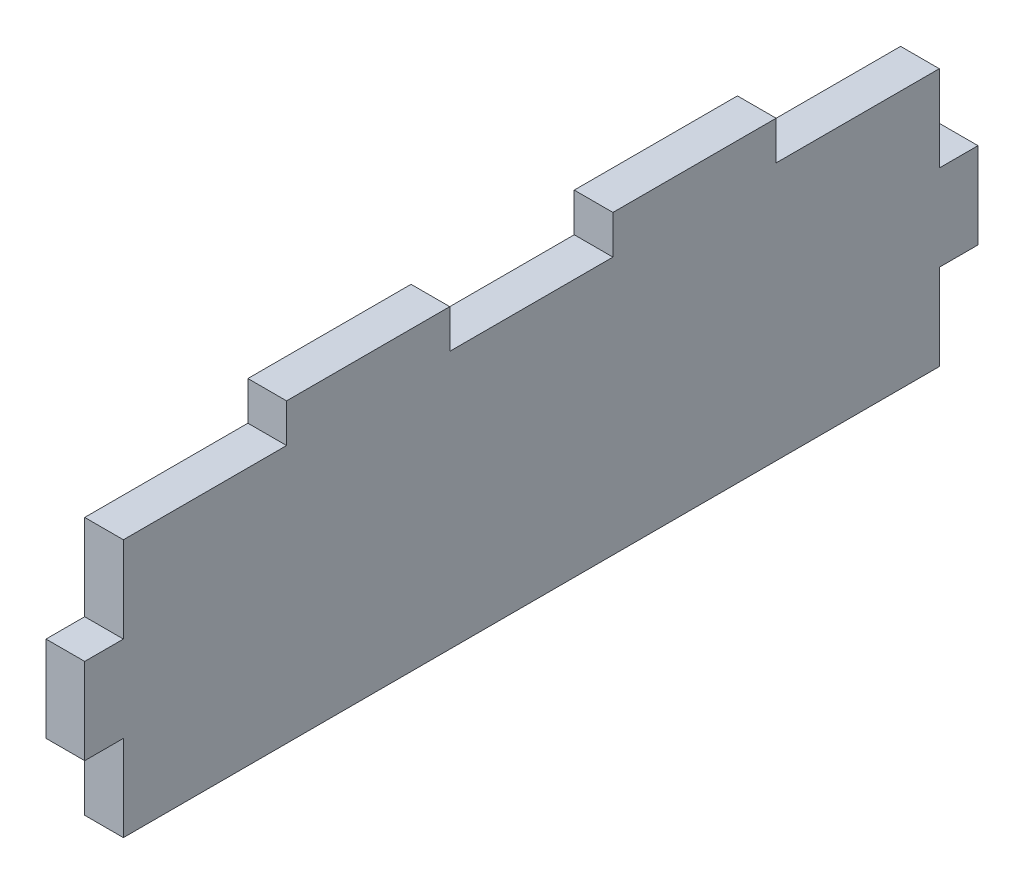
SolidWorks part; units mm, degrees
ref_plane "Front Plane" through (0, 0, 0) normal (0, 0, 1) x (1, 0, 0)
ref_plane "Top Plane" through (0, 0, 0) normal (0, 1, 0) x (1, 0, 0)
ref_plane "Right Plane" through (0, 0, 0) normal (1, 0, 0) x (0, 0, -1)
sketch "Sketch1" plane through (0, 0, 0) normal (0, 1, 0) x (1, 0, 0)
  line L1 (-207.5, -63.25) -> (207.5, -63.25)
  line L2 (-207.5, -63.25) -> (-207.5, 63.25)
  line L3 (-207.5, 63.25) -> (207.5, 63.25)
  line L4 (207.5, -63.25) -> (207.5, 63.25)
  line L5 (-207.5, -63.25) -> (207.5, 63.25) construction
  line L6 (-207.5, 63.25) -> (207.5, -63.25) construction
  point P0 (0, 0)
  dimension "D1" = 126.5
  dimension "D2" = 415
extrude "Boss-Extrude1" add sketch "Sketch1" along normal blind 6
sketch "Sketch2" plane through (0, 6, 0) normal (0, 1, 0) x (1, 0, 0)
  line L0 (213.5, -69.25) -> (213.5, 69.25)
  line L3 (-213.5, -69.25) -> (213.5, -69.25)
  line L4 (207.5, -63.25) -> (207.5, 63.25)
  line L5 (207.5, 63.25) -> (-207.5, 63.25)
  line L6 (-207.5, 63.25) -> (-207.5, -63.25)
  line L7 (-207.5, -63.25) -> (207.5, -63.25)
  line L8 (207.5, -63.25) -> (207.5, 63.25)
  line L9 (207.5, 63.25) -> (-207.5, 63.25)
  line L10 (-207.5, 63.25) -> (-207.5, -63.25)
  line L11 (-207.5, -63.25) -> (207.5, -63.25)
  line L12 (231.5, -87.25) -> (231.5, 87.25)
  line L13 (231.5, 87.25) -> (-231.5, 87.25)
  line L14 (-231.5, 87.25) -> (-231.5, -87.25)
  line L15 (-231.5, -87.25) -> (231.5, -87.25)
  line L16 (237.5, -93.25) -> (237.5, 93.25)
  line L19 (-237.5, -93.25) -> (237.5, -93.25)
  line L20 (213.5, 69.25) -> (-213.5, 69.25) construction
  line L21 (-213.5, 69.25) -> (-213.5, -69.25) construction
  line L22 (-213.5, -69.25) -> (-213.5, -63.25)
  line L27 (152.5, 69.25) -> (91.5, 69.25)
  line L28 (152.5, 69.25) -> (152.5, 63.25)
  line L29 (152.5, 63.25) -> (91.5, 63.25)
  line L30 (91.5, 69.25) -> (91.5, 63.25)
  line L31 (91.5, 69.25) -> (30.5, 69.25)
  line L32 (91.5, 69.25) -> (91.5, 63.25)
  line L33 (91.5, 63.25) -> (30.5, 63.25)
  line L34 (30.5, 69.25) -> (30.5, 63.25)
  line L35 (30.5, 69.25) -> (-30.5, 69.25)
  line L36 (30.5, 69.25) -> (30.5, 63.25)
  line L37 (30.5, 63.25) -> (-30.5, 63.25)
  line L38 (-30.5, 69.25) -> (-30.5, 63.25)
  line L39 (-30.5, 69.25) -> (-91.5, 69.25)
  line L40 (-30.5, 69.25) -> (-30.5, 63.25)
  line L41 (-30.5, 63.25) -> (-91.5, 63.25)
  line L42 (-91.5, 69.25) -> (-91.5, 63.25)
  line L43 (-91.5, 69.25) -> (-152.5, 69.25)
  line L44 (-91.5, 69.25) -> (-91.5, 63.25)
  line L45 (-91.5, 63.25) -> (-152.5, 63.25)
  line L46 (-152.5, 69.25) -> (-152.5, 63.25)
  line L47 (-152.5, 69.25) -> (-213.5, 69.25)
  line L48 (-152.5, 69.25) -> (-152.5, 63.25)
  line L49 (-152.5, 63.25) -> (-213.5, 63.25)
  line L50 (-213.5, 69.25) -> (-213.5, 63.25)
  line L51 (-213.5, 63.25) -> (-207.5, 63.25)
  line L52 (-213.5, 63.25) -> (-213.5, 37.95)
  line L53 (-213.5, 37.95) -> (-207.5, 37.95)
  line L54 (-207.5, 63.25) -> (-207.5, 37.95)
  line L55 (-207.5, 37.95) -> (-213.5, 37.95)
  line L56 (-207.5, 37.95) -> (-207.5, 12.65)
  line L57 (-207.5, 12.65) -> (-213.5, 12.65)
  line L58 (-213.5, 37.95) -> (-213.5, 12.65)
  line L59 (-213.5, 12.65) -> (-207.5, 12.65)
  line L60 (-213.5, 12.65) -> (-213.5, -12.65)
  line L61 (-213.5, -12.65) -> (-207.5, -12.65)
  line L62 (-207.5, 12.65) -> (-207.5, -12.65)
  line L63 (-207.5, -12.65) -> (-213.5, -12.65)
  line L64 (-207.5, -12.65) -> (-207.5, -37.95)
  line L65 (-207.5, -37.95) -> (-213.5, -37.95)
  line L66 (-213.5, -12.65) -> (-213.5, -37.95)
  line L67 (-213.5, -37.95) -> (-207.5, -37.95)
  line L68 (-213.5, -37.95) -> (-213.5, -63.25)
  line L69 (-213.5, -63.25) -> (-207.5, -63.25)
  line L70 (-207.5, -37.95) -> (-207.5, -63.25)
  line L71 (152.5, 63.25) -> (213.5, 63.25)
  line L72 (152.5, 63.25) -> (152.5, 69.25)
  line L73 (152.5, 69.25) -> (213.5, 69.25)
  line L74 (213.5, 63.25) -> (213.5, 69.25)
  line L75 (-237.5, 93.25) -> (-231.5, 93.25)
  line L76 (-237.5, 93.25) -> (-237.5, 55.95)
  line L77 (-237.5, 55.95) -> (-231.5, 55.95)
  line L78 (-231.5, 93.25) -> (-231.5, 55.95)
  line L79 (-237.5, 93.25) -> (-237.5, -93.25) construction
  line L80 (-231.5, 55.95) -> (-237.5, 55.95)
  line L81 (-231.5, 55.95) -> (-231.5, 18.65)
  line L82 (-231.5, 18.65) -> (-237.5, 18.65)
  line L83 (-237.5, 55.95) -> (-237.5, 18.65)
  line L84 (-237.5, 18.65) -> (-231.5, 18.65)
  line L85 (-237.5, 18.65) -> (-237.5, -18.65)
  line L86 (-237.5, -18.65) -> (-231.5, -18.65)
  line L87 (-231.5, 18.65) -> (-231.5, -18.65)
  line L88 (-231.5, -18.65) -> (-237.5, -18.65)
  line L89 (-231.5, -18.65) -> (-231.5, -55.95)
  line L90 (-231.5, -55.95) -> (-237.5, -55.95)
  line L91 (-237.5, -18.65) -> (-237.5, -55.95)
  line L92 (-237.5, -55.95) -> (-231.5, -55.95)
  line L93 (-237.5, -55.95) -> (-237.5, -93.25)
  line L94 (-237.5, -93.25) -> (-231.5, -93.25)
  line L95 (-231.5, -55.95) -> (-231.5, -93.25)
  line L96 (231.5, 87.25) -> (165.3571, 87.25)
  line L97 (231.5, 87.25) -> (231.5, 93.25)
  line L98 (231.5, 93.25) -> (165.3571, 93.25)
  line L99 (165.3571, 87.25) -> (165.3571, 93.25)
  line L100 (165.3571, 93.25) -> (99.2143, 93.25)
  line L101 (165.3571, 93.25) -> (165.3571, 87.25)
  line L102 (165.3571, 87.25) -> (99.2143, 87.25)
  line L103 (99.2143, 93.25) -> (99.2143, 87.25)
  line L104 (99.2143, 87.25) -> (33.0714, 87.25)
  line L105 (99.2143, 87.25) -> (99.2143, 93.25)
  line L106 (99.2143, 93.25) -> (33.0714, 93.25)
  line L107 (33.0714, 87.25) -> (33.0714, 93.25)
  line L108 (33.0714, 93.25) -> (-33.0714, 93.25)
  line L109 (33.0714, 93.25) -> (33.0714, 87.25)
  line L110 (33.0714, 87.25) -> (-33.0714, 87.25)
  line L111 (-33.0714, 93.25) -> (-33.0714, 87.25)
  line L112 (-33.0714, 87.25) -> (-99.2143, 87.25)
  line L113 (-33.0714, 87.25) -> (-33.0714, 93.25)
  line L114 (-33.0714, 93.25) -> (-99.2143, 93.25)
  line L115 (-99.2143, 87.25) -> (-99.2143, 93.25)
  line L116 (-99.2143, 93.25) -> (-165.3571, 93.25)
  line L117 (-99.2143, 93.25) -> (-99.2143, 87.25)
  line L118 (-99.2143, 87.25) -> (-165.3571, 87.25)
  line L119 (-165.3571, 93.25) -> (-165.3571, 87.25)
  line L120 (-165.3571, 87.25) -> (-231.5, 87.25)
  line L121 (-165.3571, 87.25) -> (-165.3571, 93.25)
  line L122 (-165.3571, 93.25) -> (-231.5, 93.25)
  line L123 (-231.5, 87.25) -> (-231.5, 93.25)
  line L124 (237.5, 93.25) -> (-237.5, 93.25) construction
  line L125 (237.5, 93.25) -> (231.5, 93.25)
  line M94 (-207.5, 63.25) -> (-207.5, -63.25)
  dimension "D1" = 0
  dimension "D2" = 6
  dimension "D3" = 18
  dimension "D4" = 6
extrude "Boss-Extrude2" add sketch "Sketch2" against normal blind 40 contours L52 L53 L49 M94 | L53 L58 L57 L10 | L60 L61 L57 M94 | L61 L66 L65 L10 | L68 L69 L65 M94 region at (-210.5, 6, 50.6) region at (-210.5, 6, 25.3) region at (-210.5, 6, 0) region at (-210.5, 6, -25.3) region at (-210.5, 6, -50.6)
extrude "Cut-Extrude1" cut sketch "Sketch1<2>" against normal through all both and the other way through all
sketch "Sketch1<2>" plane through (0, 0, 0) normal (0, 1, 0) x (1, 0, 0) same geometry as "Sketch1"
extrude "Boss-Extrude3" add sketch "Sketch2<4>" along normal blind 6 contours L61 L66 L65 L10 | L53 L58 L57 L10 region at (-210.5, 6, 25.3) region at (-210.5, 6, -25.3)
sketch "Sketch2<4>" plane through (0, 6, 0) normal (0, 1, 0) x (1, 0, 0) same geometry as "Sketch2"
sketch "Sketch6" plane through (0, 0, 63.25) normal (0, 0, 1) x (1, 0, 0)
  line L0 (-213.5, -34) -> (-213.5, 6) construction
  line L1 (-207.5, 6) -> (-213.5, 6)
  line L2 (-207.5, 6) -> (-207.5, -7.3333)
  line L3 (-207.5, -7.3333) -> (-213.5, -7.3333)
  line L4 (-213.5, 6) -> (-213.5, -7.3333)
  line L5 (-207.5, -34) -> (-207.5, 6) construction
  line L6 (-213.5, -7.3333) -> (-207.5, -7.3333)
  line L7 (-213.5, -7.3333) -> (-213.5, -20.6667)
  line L8 (-213.5, -20.6667) -> (-207.5, -20.6667)
  line L9 (-207.5, -7.3333) -> (-207.5, -20.6667)
  line L11 (-207.5, -20.6667) -> (-213.5, -20.6667)
  line L12 (-207.5, -20.6667) -> (-207.5, -34)
  line L13 (-207.5, -34) -> (-213.5, -34)
  line L14 (-213.5, -20.6667) -> (-213.5, -34)
  line M10 (-207.5, -34) -> (-207.5, 6)
  line M12 (-213.5, 6) -> (-213.5, -34)
extrude "Boss-Extrude5" add sketch "Sketch6" along normal blind 6 contours L8 L3 M12 M10 region at (-210.5, -14, 63.25)
mirror "Mirror4" about plane through (0, 0, 0) normal (0, 0, 1) of "Boss-Extrude5"
